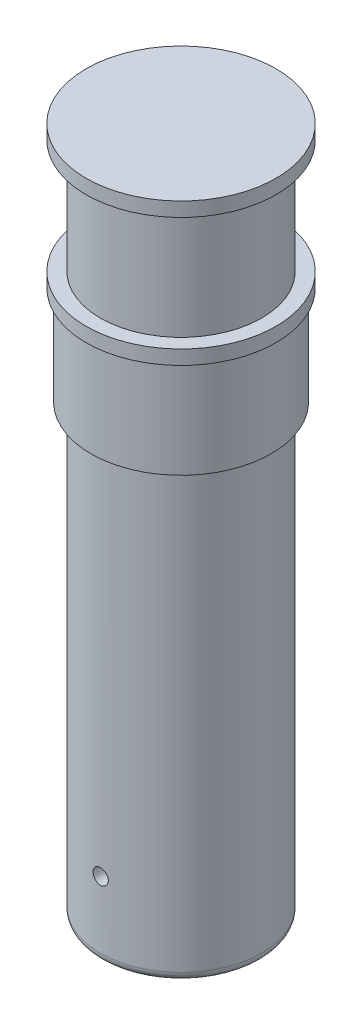
SolidWorks part; units mm, degrees
material "ABS"
ref_plane "Front Plane" through (0, 0, 0) normal (0, 0, 1) x (1, 0, 0)
ref_plane "Top Plane" through (0, 0, 0) normal (0, 1, 0) x (1, 0, 0)
ref_plane "Right Plane" through (0, 0, 0) normal (1, 0, 0) x (0, 0, -1)
sketch "Sketch1" plane through (0, 0, 0) normal (0, 0, 1) x (1, 0, 0)
  line L2 (-8.5, -57.425) -> (-8.5, -10.375)
  line L3 (-9.5, 0) -> (-10, 0)
  line L4 (-10, 0) -> (-10, 1.5)
  line L5 (-10, 1.5) -> (-8.5, 1.5)
  line L6 (-8.5, 1.5) -> (-8.5, 13.5)
  line L7 (-8.5, 13.5) -> (-10, 13.5)
  line L8 (-10, 13.5) -> (-10, 15)
  line L9 (-10, 15) -> (0, 15)
  line L10 (0, 15) -> (0, -43.425)
  line L11 (-4, -57.425) -> (-8.5, -57.425)
  line L12 (-4, -43.425) -> (-4, -57.425)
  line L13 (0, -43.425) -> (-4, -43.425)
  line L14 (-8.5, -10.375) -> (-9.5, -10.375)
  line L15 (-9.5, -10.375) -> (-9.5, 0)
  dimension "D1" = 8.5
  dimension "D2" = 1.5
  dimension "D3" = 57.425
  dimension "D4" = 1.5
  dimension "D5" = 4
  dimension "D6" = 14
  dimension "D7" = 15
  dimension "D8" = 10
  dimension "D9" = 47.05
  dimension "D10" = 1
revolve "Revolve1" add sketch "Sketch1" angle 360 about L10
fillet "Fillet1" radius 1 2 edges at (-8.5, -57.425, 0) (-4, -57.425, 0)
hole_wizard "M2x0.4 Tapped Hole1" positions "Sketch2" profile "Sketch3" tap size "M2x0.4" standard "ANSI Metric" end condition up to next
sketch "Sketch2" plane through (0, 0, 0) normal (0, 0, 1) x (1, 0, 0)
  line L0 (-7.5, -57.425) -> (7.5, -57.425) construction
  point P0 (0, -49.425)
  dimension "D1" = 8
sketch "Sketch3" plane through (0, -49.425, 0) normal (1, 0, 0) x (0, 1, 0)
  line L0 (0, 0) -> (0, 8.5)
  line L1 (0, 8.5) -> (0.8, 8.5)
  line L2 (0.8, 8.5) -> (0.8, 0)
  line L5 (0.8, 0) -> (0, 0)
  line L11 (0, -6.35) -> (0, 107.95) construction
  dimension "Thru Tap Drill Dia." = 1.6
  dimension "Thru Tap Drill Depth" = 8.5
cosmetic thread "Hole Thread1" parameters "D2"=2
